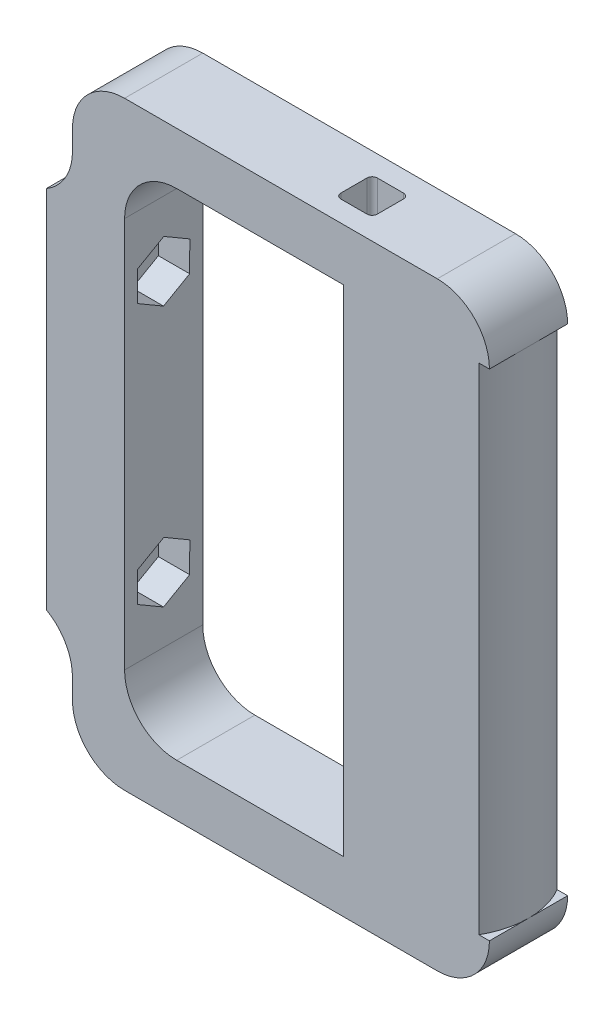
SolidWorks part; units mm, degrees
material "ABS"
ref_plane "Front Plane" through (0, 0, 0) normal (0, 0, 1) x (1, 0, 0)
ref_plane "Top Plane" through (0, 0, 0) normal (0, 1, 0) x (1, 0, 0)
ref_plane "Right Plane" through (0, 0, 0) normal (1, 0, 0) x (0, 0, -1)
sketch "Model" plane through (0, 0, 0) normal (0, 0, 1) x (1, 0, 0)
  line L0 (80, 115) -> (80, 105)
  line L1 (80, 0) -> (80, 10)
  line L8 (-5, 92.5) -> (0, 92.5)
  line L9 (-5, 22.5) -> (0, 22.5)
  line L10 (-5, 92.5) -> (-5, 22.5)
  line L11 (0, 115) -> (80, 115)
  line L12 (0, 0) -> (80, 0)
  line L13 (80, 105) -> (10, 105)
  line L14 (80, 10) -> (10, 10)
  line L16 (10, 105) -> (10, 10)
  line L17 (0, 115) -> (0, 92.5)
  line L19 (0, 0) -> (0, 22.5)
  dimension "D1" = 10
  dimension "D2" = 10
  dimension "D3" = 5
  dimension "D4" = 10
  dimension "D5" = 10
  dimension "D6" = 70
  dimension "D7" = 70
  dimension "D8" = 22.5
  dimension "D9" = 70
  dimension "D10" = 22.5
extrude "Boss-Extrude1" add sketch "Model" along normal blind 15
sketch "Sketch2" plane through (-5, 0, 0) normal (-1, 0, 0) x (0, 0, 1)
  line L0 (15, 92.5) -> (0, 92.5) construction
  line L1 (0, 92.5) -> (0, 22.5) construction
  circle A0 centre (7.5, 82.5) radius 3
  circle A1 centre (7.5, 32.5) radius 3
  point P2 (7.5, 92.5)
  dimension "D1" = 10
  dimension "D3" = 6
  dimension "D4" = 6
  dimension "D2" = 7.5
  dimension "D5" = 50
  dimension "D6" = 7.5
extrude "Cut-Extrude4" cut sketch "Sketch2" against normal up to next
sketch "Sketch6" plane through (0, 105, 0) normal (0, -1, 0) x (1, 0, 0)
  line L1 (52.0096, 15) -> (77.9904, 15)
  line L2 (52.0096, 0) -> (77.9904, 0)
  line L3 (10, 15) -> (80, 15) construction
  line L4 (10, 0) -> (80, 0) construction
  line L5 (10, 15) -> (10, 0) construction
  line L6 (80, 15) -> (80, 0) construction
  arc A0 (52.0096, 15) -> (52.0096, 0) centre (65, 7.5) ccw
  arc A1 (77.9904, 15) -> (77.9904, 0) centre (65, 7.5) cw
  dimension "D3" = 15
  dimension "D4" = 15
  dimension "D5" = 15
  dimension "D2" = 7.5
extrude "Boss-Extrude2" add sketch "Sketch6" along normal up to next
sketch "Sketch8" plane through (0, 115, 0) normal (0, 1, 0) x (1, 0, 0)
  line L0 (80, -15) -> (80, 0) construction
  line L2 (80, 0) -> (0, 0) construction
  line L3 (46.5, -4) -> (53.5, -4)
  line L4 (46.5, -4) -> (46.5, -11)
  line L5 (46.5, -11) -> (53.5, -11)
  line L6 (53.5, -4) -> (53.5, -11)
  line L7 (46.5, -4) -> (53.5, -11) construction
  line L8 (46.5, -11) -> (53.5, -4) construction
  dimension "D1" = 7
  dimension "D2" = 7
  dimension "D3" = 26.5
  dimension "D4" = 4
extrude "Cut-Extrude6" cut sketch "Sketch8" against normal blind 7
sketch "Sketch9" plane through (0, 108, 0) normal (0, 1, 0) x (1, 0, 0)
  line L4 (46.5, -4) -> (46.5, -11) construction
  line L5 (46.5, -11) -> (53.5, -11) construction
  circle A0 centre (50, -7.5) radius 2
  point P3 (46.5, -7.5)
  point P5 (2447.7738, -7.7966)
  dimension "D1" = 4
  dimension "D2" = 3.5
  dimension "D3" = 3.5
extrude "Cut-Extrude7" cut sketch "Sketch9" against normal blind 3
fillet "Fillet5" radius 10 8 edges at (80, 115, 7.5) (80, 0, 7.5) (0, 0, 7.5) (0, 22.5, 7.5) (10, 10, 7.5) (10, 105, 7.5) (0, 92.5, 7.5) (0, 115, 7.5)
sketch "Sketch13" plane through (0, 0, 0) normal (0, 0, -1) x (-1, 0, 0)
  line L0 (-70, 115) -> (-10, 115) construction
  line L2 (-13.5, 112) -> (-6.5, 112)
  line L3 (-13.5, 112) -> (-13.5, 105)
  line L4 (-13.5, 105) -> (-6.5, 105)
  line L5 (-6.5, 112) -> (-6.5, 105)
  line L6 (-13.5, 112) -> (-6.5, 105) construction
  line L7 (-13.5, 105) -> (-6.5, 112) construction
  line L8 (0, 105) -> (0, 101.1603) construction
  point P3 (-10, 108.5)
  dimension "D1" = 7
  dimension "D2" = 7
  dimension "D3" = 3
  dimension "D4" = 6.5
extrude "Cut-Extrude9" cut sketch "Sketch13" against normal blind 10
fillet "Fillet6" radius 1 8 edges at (53.5, 111.5, 4) (53.5, 111.5, 11) (46.5, 111.5, 4) (46.5, 111.5, 11) (6.5, 105, 5) (13.5, 105, 5) (13.5, 112, 5) (6.5, 112, 5)
ref_plane "Plane2" through (10, 0, 0) normal (1, 0, 0) x (0, 0, -1)
sketch "Sketch16" plane through (10, 0, 0) normal (1, 0, 0) x (0, 0, -1)
  line L0 (0, 95) -> (-15, 95) construction
  circle A0 centre (-7.5, 105) radius 2
  point P0 (-7.5, 95)
  dimension "D1" = 10
  dimension "D2" = 4
  dimension "D3" = 7.5
extrude "Cut-Extrude12" cut sketch "Sketch16" against normal mid plane 80
sketch "Sketch17" plane through (10, 0, 0) normal (1, 0, 0) x (0, 0, -1)
  line L1 (-7.4735, 88.2734) -> (-12.4867, 85.4097)
  line L2 (-12.4867, 85.4097) -> (-12.5132, 79.6362)
  line L3 (-12.5132, 79.6362) -> (-7.5265, 76.7266)
  line L4 (-7.5265, 76.7266) -> (-2.5133, 79.5903)
  line L5 (-2.5133, 79.5903) -> (-2.4868, 85.3638)
  line L6 (-2.4868, 85.3638) -> (-7.4735, 88.2734)
  line L7 (-7.4735, 38.2734) -> (-12.4867, 35.4097)
  line L8 (-12.4867, 35.4097) -> (-12.5132, 29.6362)
  line L9 (-12.5132, 29.6362) -> (-7.5265, 26.7266)
  line L10 (-7.5265, 26.7266) -> (-2.5133, 29.5903)
  line L11 (-2.5133, 29.5903) -> (-2.4868, 35.3638)
  line L12 (-2.4868, 35.3638) -> (-7.4735, 38.2734)
  line L14 (0, 20) -> (0, 95) construction
  line L15 (0, 95) -> (-15, 95) construction
  circle A0 centre (-7.5, 82.5) radius 5 construction
  circle A1 centre (-7.5, 32.5) radius 5 construction
  dimension "D1" = 10
  dimension "D2" = 10
extrude "Cut-Extrude13" cut sketch "Sketch17" against normal blind 6
